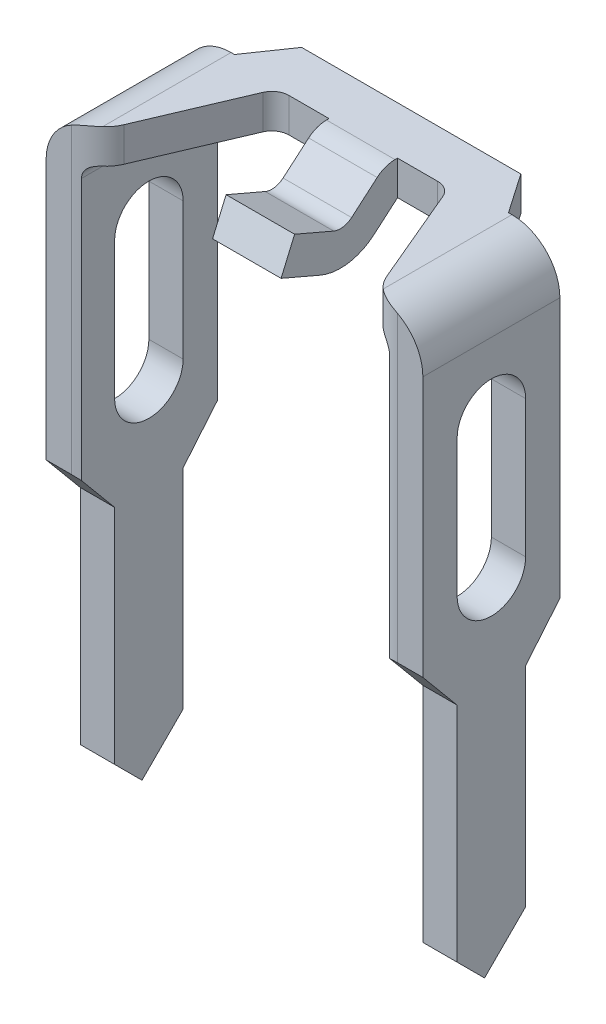
SolidWorks part; units mm, degrees
ref_plane "Front Plane" through (0, 0, 0) normal (0, 0, 1) x (1, 0, 0)
ref_plane "Top Plane" through (0, 0, 0) normal (0, 1, 0) x (1, 0, 0)
ref_plane "Right Plane" through (0, 0, 0) normal (1, 0, 0) x (0, 0, -1)
sketch "Sketch1" plane through (0, 0, 0) normal (0, 0, 1) x (1, 0, 0)
  line L0 (-2.75, -4) -> (-2.75, 4.05)
  line L1 (-2.25, -4.25) -> (-2.25, 4.25) construction
  line L2 (-2.25, -4) -> (-2.25, 4.05)
  line L3 (-2.05, 4.25) -> (2.05, 4.25)
  line L4 (2.25, -4) -> (2.25, 4.05)
  line L5 (2.2086, 4.1718) -> (2.25, 4.25) construction
  line L6 (-2.25, 4.25) -> (-2.2086, 4.1718) construction
  line L7 (-2.05, 4.75) -> (2.05, 4.75)
  line L8 (2.75, -4) -> (2.75, 4.05)
  line L9 (2.75, -4.75) -> (2.75, 4.75) construction
  line L12 (-2.75, -4.75) -> (-2.75, 4.75) construction
  line L13 (-2.25, 4.25) -> (2.25, 4.25) construction
  line L14 (-2.75, -4.75) -> (2.75, -4.75) construction
  line L15 (-2.25, -4.25) -> (2.25, -4.25) construction
  line L16 (2.25, -4.25) -> (2.25, 4.25) construction
  line L17 (-2.75, 4.75) -> (2.75, 4.75) construction
  line L18 (-2.75, -4) -> (-2.25, -4)
  line L19 (2.25, -4) -> (2.75, -4)
  arc A0 (-2.25, 4.05) -> (-2.05, 4.25) centre (-2.05, 4.05) cw
  arc A1 (2.05, 4.25) -> (2.25, 4.05) centre (2.05, 4.05) cw
  arc A2 (2.05, 4.75) -> (2.75, 4.05) centre (2.05, 4.05) cw
  arc A3 (-2.75, 4.05) -> (-2.05, 4.75) centre (-2.05, 4.05) cw
  point P0 (0, 0)
  dimension "D4" = 0.2
  dimension "D5" = 0.7
  dimension "D1" = 4.5
  dimension "D2" = 4.25
  dimension "D6" = 4
  dimension "D3" = 0.5
extrude "Boss-Extrude1" add sketch "Sketch1" along normal blind 2.58
sketch "Sketch2" plane through (0, 4.75, 0) normal (0, 1, 0) x (1, 0, 0)
  line L0 (2.05, 0) -> (-2.05, 0) construction
  line L1 (-2, -0.58) -> (-4.0994, -0.58)
  line L2 (-1.6, 0) -> (-2, 0.8334)
  line L3 (-2, 0.8334) -> (-4.0994, 0.8334)
  line L4 (-4.0994, -0.58) -> (-4.0994, 0.8334)
  line L5 (2, -0.58) -> (3.3574, -0.58)
  line L6 (1.6, 0) -> (2, 0.8334)
  line L7 (2, 0.8334) -> (3.3574, 0.8334)
  line L8 (3.3574, -0.58) -> (3.3574, 0.8334)
  line L9 (2.05, -2.58) -> (-2.05, -2.58) construction
  line L11 (-2, -0.58) -> (-1.6, 0)
  line L12 (2, -0.58) -> (1.6, 0)
  line L13 (-2.75, -2.58) -> (-2.3806, -2.58)
  line L15 (-1.9205, -2.2758) -> (-1.3147, -0.8521)
  line L16 (-1.0847, -0.7) -> (1.0843, -0.7)
  line L17 (1.3145, -0.8526) -> (1.916, -2.2748)
  line L19 (2.3765, -2.58) -> (2.75, -2.58)
  line L20 (2.75, -2.58) -> (2.75, -3.0561)
  line L21 (2.75, -3.0561) -> (-2.75, -3.0561)
  line L22 (-2.75, -3.0561) -> (-2.75, -2.58)
  arc A0 (1.916, -2.2748) -> (2.3765, -2.58) centre (2.3765, -2.08) ccw
  arc A1 (-2.3806, -2.58) -> (-1.9205, -2.2758) centre (-2.3806, -2.08) ccw
  arc A2 (1.0843, -0.7) -> (1.3145, -0.8526) centre (1.0843, -0.95) cw
  arc A3 (-1.3147, -0.8521) -> (-1.0847, -0.7) centre (-1.0847, -0.95) cw
  point P22 (-2.05, -2.58)
  point P31 (1.25, -0.7)
  point P34 (-1.25, -0.7)
  dimension "D8" = 0.5
  dimension "D9" = 0.25
  dimension "D1" = 2
  dimension "D2" = 2
  dimension "D3" = 2.5
  dimension "D4" = 1.25
  dimension "D5" = 0.4
  dimension "D6" = 0.4
  dimension "D7" = 0.7
extrude "Cut-Extrude1" cut sketch "Sketch2" against normal blind 10.5
sketch "Sketch3" plane through (0, 0, 0) normal (1, 0, 0) x (0, 0, -1)
  line L0 (-1.58, -4.25) -> (-1.58, 4.05) construction
  line L2 (-2.58, 4.05) -> (-0.58, 4.05) construction
  line L3 (-0.58, 0.25) -> (-1.08, -0.35)
  line L4 (-0.58, 4.05) -> (-0.58, -4) construction
  line L5 (-1.08, -0.35) -> (-1.08, -4.3963)
  line L6 (-1.08, -4.3963) -> (-0.1303, -4.3963)
  line L7 (-0.1303, -4.3963) -> (-0.1303, 0.25)
  line L8 (-0.1303, 0.25) -> (-0.58, 0.25)
  line L9 (-2.58, 0.25) -> (-2.08, -0.35)
  line L10 (-2.58, 4.05) -> (-2.58, -4) construction
  line L11 (-2.08, -0.35) -> (-2.08, -4.8963)
  line L12 (-2.08, -4.8963) -> (-3.0703, -4.8963)
  line L13 (-3.0703, -4.8963) -> (-3.0703, 0.25)
  line L14 (-3.0703, 0.25) -> (-2.58, 0.25)
  line L15 (-2.4551, 4.75) -> (-0.58, 4.75) construction
  line L16 (-1.58, 3.0246) -> (-1.58, 1.0246) construction
  line L17 (-1.08, 3.0246) -> (-1.08, 1.0246)
  line L18 (-2.08, 3.0246) -> (-2.08, 1.0246)
  arc A0 (-1.08, 3.0246) -> (-2.08, 3.0246) centre (-1.58, 3.0246) ccw
  arc A1 (-2.08, 1.0246) -> (-1.08, 1.0246) centre (-1.58, 1.0246) ccw
  point P22 (-1.58, 2.0246)
  dimension "D8" = 0.5
  dimension "D1" = 4.5
  dimension "D2" = 4.5
  dimension "D3" = 0.5
  dimension "D4" = 0.5
  dimension "D5" = 0.6
  dimension "D6" = 0.6
  dimension "D7" = 2
extrude "Cut-Extrude2" cut sketch "Sketch3" against normal mid plane 10.5
sketch "Sketch4" plane through (0, 0, 0) normal (1, 0, 0) x (0, 0, -1)
  line L0 (-0.7, 4.25) -> (-1.0452, 3.9541)
  line L1 (-1.8294, 3.8345) -> (-2.4, 4.0797)
  line L2 (-2.4, 4.0797) -> (-2.2026, 4.5391)
  line L3 (-2.2026, 4.5391) -> (-1.632, 4.2939)
  line L4 (-1.3706, 4.3338) -> (-0.9973, 4.6537)
  line L5 (-0.7, 4.75) -> (-0.737, 4.75)
  line L6 (-0.7, 4.75) -> (-0.7, 4.25)
  arc A0 (-0.9973, 4.6537) -> (-0.737, 4.75) centre (-0.737, 4.35) cw
  arc A1 (-1.632, 4.2939) -> (-1.3706, 4.3338) centre (-1.5333, 4.5236) ccw
  arc A2 (-1.0452, 3.9541) -> (-1.8294, 3.8345) centre (-1.5333, 4.5236) cw
  point P15 (-1.4, 3.65)
  dimension "D6" = 0.4
  dimension "D7" = 0.25
  dimension "D8" = 0.75
  dimension "D1" = 0.7
  dimension "D2" = 0.6
  dimension "D3" = 1
  dimension "D4" = 0.5
  dimension "D5" = 0.5
extrude "Boss-Extrude2" add sketch "Sketch4" along normal mid plane 1
chamfer "Chamfer1" distance 0.6 angle 45 2 edges at (-2.5, -4, 1.08) (2.5, -4, 1.08)
chamfer "Chamfer2" distance 0.4 angle 45 2 edges at (-2.5, -4, 2.08) (2.5, -4, 2.08)
